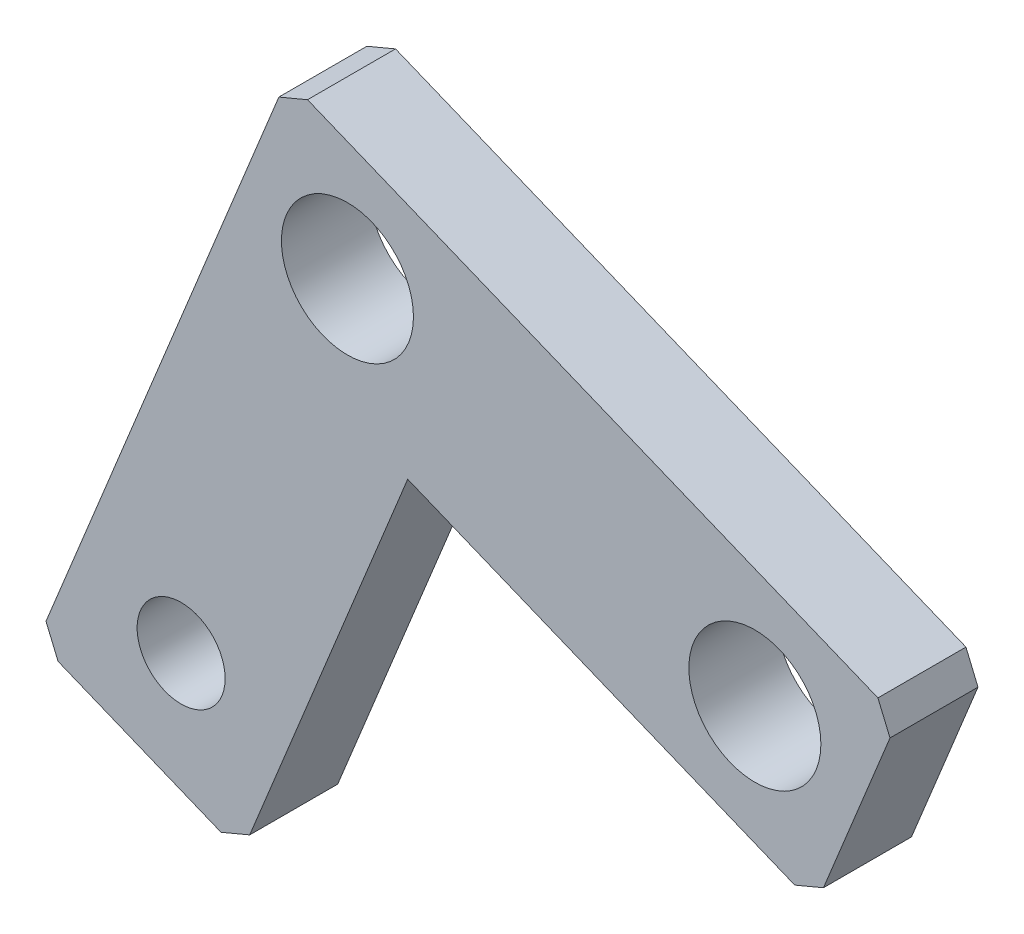
SolidWorks part; units mm, degrees
ref_plane "前基準面" through (0, 0, 0) normal (0, 0, 1) x (1, 0, 0)
ref_plane "上基準面" through (0, 0, 0) normal (0, 1, 0) x (1, 0, 0)
ref_plane "右基準面" through (0, 0, 0) normal (1, 0, 0) x (0, 0, -1)
sketch "草圖1" plane through (0, 0, 0) normal (0, 0, 1) x (1, 0, 0)
  line L0 (-42.6847, 14.9509) -> (26.7532, -13.3931)
  line L5 (26.7532, -13.3931) -> (17.3052, -36.5391)
  line L6 (17.3052, -36.5391) -> (-28.9867, -17.6431)
  line L7 (-28.9867, -17.6431) -> (-47.8827, -63.935)
  line L8 (-47.8827, -63.935) -> (-71.0287, -54.487)
  line L9 (-71.0287, -54.487) -> (-42.6847, 14.9509)
  line L10 (22.0292, -24.9661) -> (-47.4087, 3.3779) construction
  line L11 (-59.4557, -59.211) -> (-31.1117, 10.2269) construction
  circle A0 centre (10.4562, -20.2421) radius 7.5
  circle A1 centre (-35.8357, -1.3461) radius 7.5
  circle A2 centre (-54.7317, -47.638) radius 5
  point P12 (-35.8357, -1.3461)
  dimension "D5" = 15
  dimension "D8" = 15
  dimension "D9" = 10
  dimension "D1" = 25
  dimension "D2" = 25
  dimension "D3" = 75
  dimension "D4" = 75
  dimension "D6" = 12.5
  dimension "D7" = 12.5
  dimension "D10" = 12.5
extrude "填料-伸長1" add sketch "草圖1" against normal blind 10
chamfer "導角1" distance 2.5 angle 45 5 edges at (-47.8827, -63.935, -5) (17.3052, -36.5391, -5) (26.7532, -13.3931, -5) (-71.0287, -54.487, -5) (-42.6847, 14.9509, -5)
